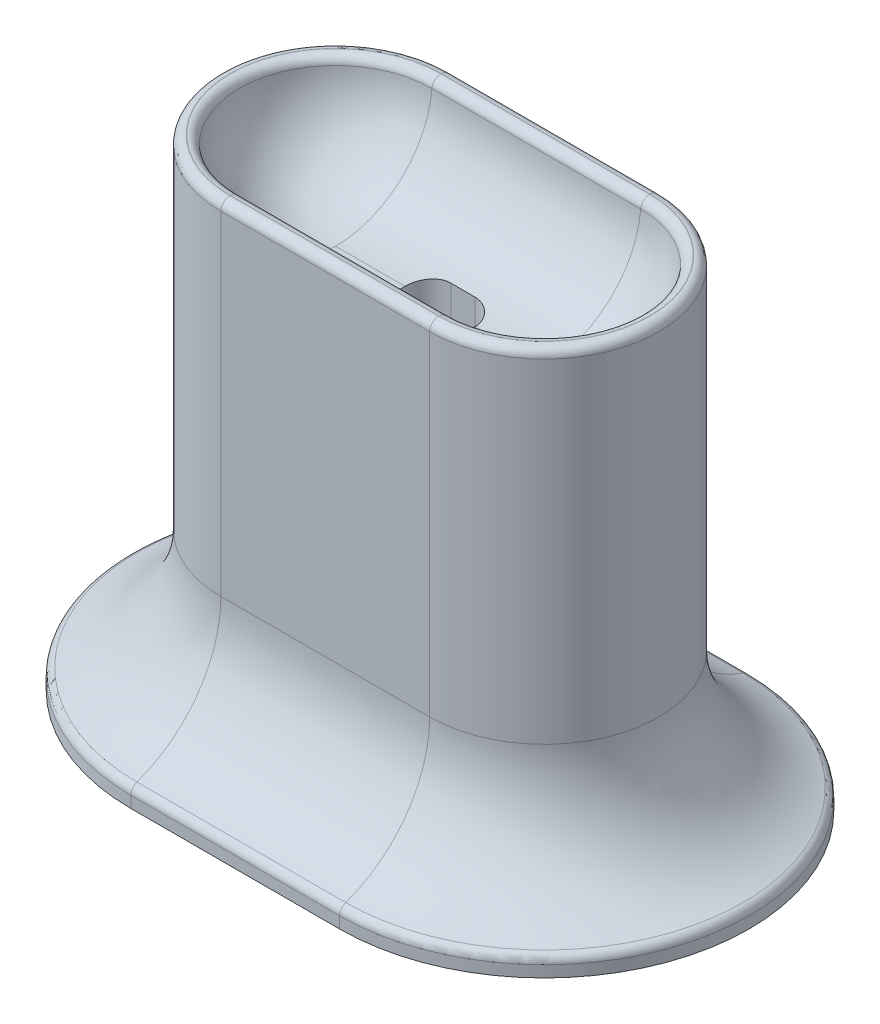
SolidWorks part; units mm, degrees
ref_plane "Front Plane" through (0, 0, 0) normal (0, 0, 1) x (1, 0, 0)
ref_plane "Top Plane" through (0, 0, 0) normal (0, 1, 0) x (1, 0, 0)
ref_plane "Right Plane" through (0, 0, 0) normal (1, 0, 0) x (0, 0, -1)
sketch "Sketch2" plane through (0, 0, 0) normal (0, 1, 0) x (1, 0, 0)
  line L0 (0, 10.75) -> (23.2, 10.75)
  line L1 (0, -10.75) -> (23.2, -10.75)
  line L2 (0, -12.75) -> (23.2, -12.75)
  line L3 (0, 12.75) -> (23.2, 12.75)
  line L4 (0, 22.75) -> (23.2, 22.75)
  line L5 (0, -22.75) -> (23.2, -22.75)
  arc A0 (0, 10.75) -> (0, -10.75) centre (0, 0) ccw
  arc A1 (23.2, -10.75) -> (23.2, 10.75) centre (23.2, 0) ccw
  arc A2 (0, 12.75) -> (0, -12.75) centre (0, 0) ccw
  arc A3 (23.2, -12.75) -> (23.2, 12.75) centre (23.2, 0) ccw
  arc A4 (23.2, -22.75) -> (23.2, 22.75) centre (23.2, 0) ccw
  arc A5 (0, 22.75) -> (0, -22.75) centre (0, 0) ccw
  dimension "D1" = 21.5
  dimension "D2" = 23.2
  dimension "D3" = 2
  dimension "D4" = 10
extrude "Boss-Extrude1" add sketch "Sketch2" along normal blind 53.5 contours L2 A3 L3 A2 A1 L1 A0 L0 region at (-12.2003, 0, 0)
extrude "Boss-Extrude2" add sketch "Sketch2<3>" against normal blind 10 from offset 42.75 contours L1 A1 L0 A0 region at (11.6, 0, 0)
sketch "Sketch2<3>" plane through (0, 0, 0) normal (0, 1, 0) x (1, 0, 0) same geometry as "Sketch2"
extrude "Boss-Extrude3" add sketch "Sketch2<4>" along normal blind 2 contours L4 A5 L5 A4 A3 L2 A2 L3 region at (11.6, 0, -21.926)
sketch "Sketch2<4>" plane through (0, 0, 0) normal (0, 1, 0) x (1, 0, 0) same geometry as "Sketch2"
fillet "Fillet1" radius 10.75 4 edges at (11.6, 42.75, -10.75) (33.95, 42.75, 0) (11.6, 42.75, 10.75) (-10.75, 42.75, 0)
fillet "Fillet2" radius 14 4 edges at (-12.75, 2, 0) (11.6, 2, -12.75) (35.95, 2, 0) (11.6, 2, 12.75)
fillet "Fillet3" radius 1 12 edges at (-22.75, 2, 0) (11.6, 2, 22.75) (45.95, 2, 0) (-10.75, 53.5, 0) (11.6, 53.5, 10.75) (33.95, 53.5, 0) (-12.75, 53.5, 0) (11.6, 53.5, 12.75) (35.95, 53.5, 0) (11.6, 2, -22.75) (11.6, 53.5, -10.75) (11.6, 53.5, -12.75)
sketch "Sketch3" plane through (0, 32.75, 0) normal (0, -1, 0) x (1, 0, 0)
  line L2 (0, 0) -> (23.2, 0) construction
  line L4 (11.6, -2.7653) -> (11.6, -2.55) construction
  line L5 (12.95, 2.55) -> (10.25, 2.55)
  line L6 (12.95, -2.55) -> (10.25, -2.55)
  line L7 (11.6, 2.55) -> (11.6, 3.8053) construction
  arc A3 (10.25, 2.55) -> (10.25, -2.55) centre (10.25, 0) ccw
  arc A4 (12.95, 2.55) -> (12.95, -2.55) centre (12.95, 0) cw
  point P11 (11.6, 0)
  dimension "D2" = 5.1
sketch "Sketch4" plane through (0, 0, -10.75) normal (0, 0, 1) x (1, 0, 0)
  line L14 (11.6, 0) -> (12.85, 0)
  line L15 (0, 0) -> (23.2, 0) construction
  line L16 (11.6, 0) -> (10.35, 0)
  line L17 (12.85, 0) -> (12.85, 2.0022)
  line L18 (10.35, 0) -> (10.35, 2.0022)
  arc A3 (12.85, 2.0022) -> (10.35, 2.0022) centre (11.6, 2.8313) ccw
  point P10 (11.6, 2.8313)
  dimension "D1" = 3
  dimension "D2" = 1.25
  dimension "D3" = 1.25
extrude "Cut-Extrude4" cut sketch "Sketch4" against normal through all
extrude "Cut-Extrude5" cut sketch "Sketch3" against normal through all both and the other way through all
